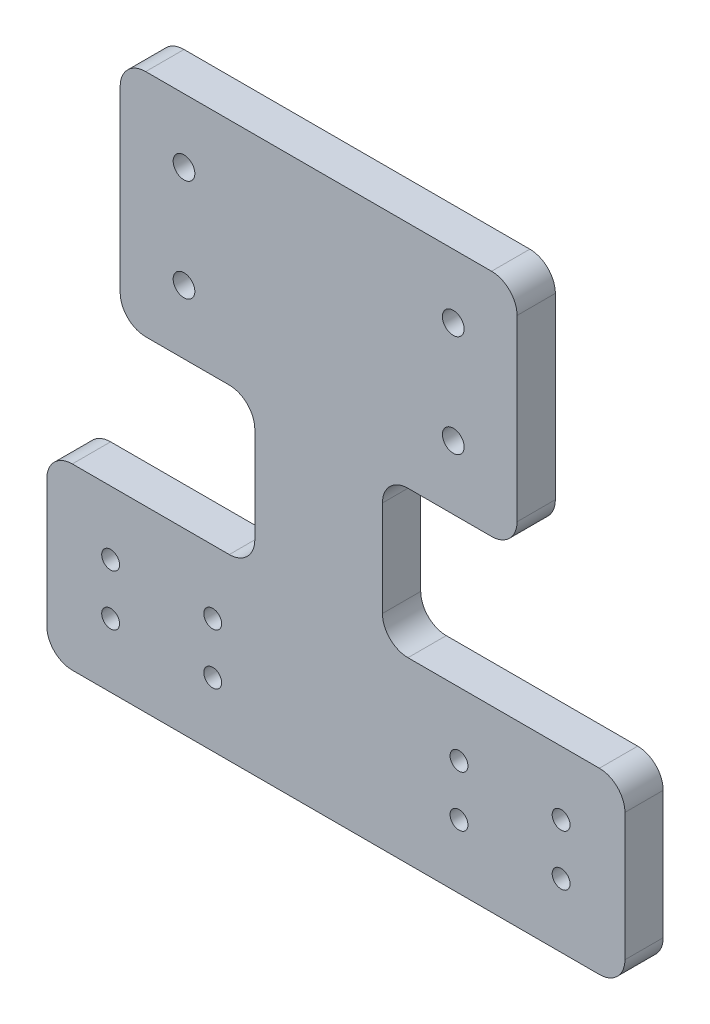
SolidWorks part; units mm, degrees
ref_plane "Front Plane" through (0, 0, 0) normal (0, 0, 1) x (1, 0, 0)
ref_plane "Top Plane" through (0, 0, 0) normal (0, 1, 0) x (1, 0, 0)
ref_plane "Right Plane" through (0, 0, 0) normal (1, 0, 0) x (0, 0, -1)
sketch "Sketch1" plane through (0, 0, 0) normal (0, 0, 1) x (1, 0, 0)
  line L0 (28.1, 15) -> (-28.1, 15) construction
  line L1 (-28.1, -15) -> (28.1, 15) construction
  line L2 (-28.1, 15) -> (-28.1, -15) construction
  line L3 (-28.1, -15) -> (28.1, -15) construction
  line L4 (-50, 20) -> (50, 20)
  line L5 (28.1, 15) -> (28.1, -15) construction
  line L6 (-50, 20) -> (-50, -80)
  line L7 (-50, -80) -> (50, -80)
  line L8 (50, 20) -> (50, -80)
  line L9 (-28.1, 15) -> (28.1, -15) construction
  line L10 (-50, 20) -> (50, -80) construction
  line L12 (-50, -80) -> (50, 20) construction
  dimension "D4" = 30
  dimension "D5" = 50
  dimension "D2" = 50
  dimension "D1" = 20
  dimension "D3" = 56.2
  dimension "D6" = 80
extrude "Boss-Extrude1" add sketch "Sketch1" along normal blind 6
sketch "Sketch2" plane through (0, 0, 0) normal (0, 0, 1) x (1, 0, 0)
  line L0 (28.1, 15) -> (-28.1, 15) construction
  line L1 (-28.1, -15) -> (28.1, 15) construction
  line L2 (-28.1, 15) -> (-28.1, -15) construction
  line L3 (-28.1, -15) -> (28.1, -15) construction
  line L4 (28.1, 15) -> (28.1, -15) construction
  line L5 (-28.1, 15) -> (28.1, -15) construction
  line L6 (-28.1, 0) -> (28.1, 0) construction
  line L7 (-17.9015, 8) -> (-19.5007, 10.77)
  line L8 (-19.5007, 10.77) -> (-22.6993, 10.77)
  line L9 (-22.6993, 10.77) -> (-24.2985, 8)
  line L10 (-24.2985, 8) -> (-22.6993, 5.23)
  line L11 (-22.6993, 5.23) -> (-19.5007, 5.23)
  line L12 (-19.5007, 5.23) -> (-17.9015, 8)
  line L13 (19.5007, 5.23) -> (17.9015, 8)
  line L14 (0, 15) -> (0, -15) construction
  line L15 (22.6993, 5.23) -> (19.5007, 5.23)
  line L16 (24.2985, 8) -> (22.6993, 5.23)
  line L17 (22.6993, 10.77) -> (24.2985, 8)
  line L18 (19.5007, 10.77) -> (22.6993, 10.77)
  line L19 (17.9015, 8) -> (19.5007, 10.77)
  line L20 (17.9015, -8) -> (19.5007, -10.77)
  line L21 (19.5007, -10.77) -> (22.6993, -10.77)
  line L22 (22.6993, -10.77) -> (24.2985, -8)
  line L23 (24.2985, -8) -> (22.6993, -5.23)
  line L24 (22.6993, -5.23) -> (19.5007, -5.23)
  line L25 (19.5007, -5.23) -> (17.9015, -8)
  line L26 (-19.5007, -5.23) -> (-17.9015, -8)
  line L27 (-22.6993, -5.23) -> (-19.5007, -5.23)
  line L28 (-24.2985, -8) -> (-22.6993, -5.23)
  line L29 (-22.6993, -10.77) -> (-24.2985, -8)
  line L30 (-19.5007, -10.77) -> (-22.6993, -10.77)
  line L31 (-17.9015, -8) -> (-19.5007, -10.77)
  circle A0 centre (-21.1, 8) radius 2.77 construction
  circle A1 centre (21.1, 8) radius 2.77 construction
  circle A2 centre (21.1, -8) radius 2.77 construction
  circle A3 centre (-21.1, -8) radius 2.77 construction
  dimension "D3" = 5.54
  dimension "D1" = 56.2
  dimension "D2" = 30
extrude "Cut-Extrude1" cut sketch "Sketch2" along normal blind 2.5
sketch "Sketch3" plane through (0, 0, 0) normal (0, 0, -1) x (-1, 0, 0)
  line L0 (28.1, 15) -> (-28.1, 15) construction
  line L1 (-28.1, -15) -> (28.1, 15) construction
  line L2 (-28.1, 15) -> (-28.1, -15) construction
  line L3 (-28.1, -15) -> (28.1, -15) construction
  line L4 (28.1, 15) -> (28.1, -15) construction
  line L5 (-28.1, 15) -> (28.1, -15) construction
  line L6 (-28.1, 0) -> (28.1, 0) construction
  line L7 (-17.9015, 8) -> (-19.5007, 10.77) construction
  line L8 (-19.5007, 10.77) -> (-22.6993, 10.77) construction
  line L9 (-22.6993, 10.77) -> (-24.2985, 8) construction
  line L10 (-24.2985, 8) -> (-22.6993, 5.23) construction
  line L11 (-22.6993, 5.23) -> (-19.5007, 5.23) construction
  line L12 (-19.5007, 5.23) -> (-17.9015, 8) construction
  line L13 (19.5007, 5.23) -> (17.9015, 8) construction
  line L14 (0, 15) -> (0, -15) construction
  line L15 (22.6993, 5.23) -> (19.5007, 5.23) construction
  line L16 (24.2985, 8) -> (22.6993, 5.23) construction
  line L17 (22.6993, 10.77) -> (24.2985, 8) construction
  line L18 (19.5007, 10.77) -> (22.6993, 10.77) construction
  line L19 (17.9015, 8) -> (19.5007, 10.77) construction
  line L20 (17.9015, -8) -> (19.5007, -10.77) construction
  line L21 (19.5007, -10.77) -> (22.6993, -10.77) construction
  line L22 (22.6993, -10.77) -> (24.2985, -8) construction
  line L23 (24.2985, -8) -> (22.6993, -5.23) construction
  line L24 (22.6993, -5.23) -> (19.5007, -5.23) construction
  line L25 (19.5007, -5.23) -> (17.9015, -8) construction
  line L26 (-19.5007, -5.23) -> (-17.9015, -8) construction
  line L27 (-22.6993, -5.23) -> (-19.5007, -5.23) construction
  line L28 (-24.2985, -8) -> (-22.6993, -5.23) construction
  line L29 (-22.6993, -10.77) -> (-24.2985, -8) construction
  line L30 (-19.5007, -10.77) -> (-22.6993, -10.77) construction
  line L31 (-17.9015, -8) -> (-19.5007, -10.77) construction
  circle A0 centre (-21.1, 8) radius 2.77 construction
  circle A1 centre (21.1, 8) radius 2.77 construction
  circle A2 centre (21.1, -8) radius 2.77 construction
  circle A3 centre (-21.1, -8) radius 2.77 construction
  circle A4 centre (-21.1, 8) radius 1.7
  circle A5 centre (21.1, 8) radius 1.7
  circle A6 centre (21.1, -8) radius 1.7
  circle A7 centre (-21.1, -8) radius 1.7
  dimension "D3" = 5.54
  dimension "D4" = 3.4
  dimension "D1" = 56.2
  dimension "D2" = 30
extrude "Cut-Extrude2" cut sketch "Sketch3" against normal up to surface (6 mm away) up to face at (0, -30, 6)
sketch "Sketch4" plane through (0, 0, 0) normal (0, 0, -1) x (-1, 0, 0)
  line L0 (-30, -29) -> (-30, -51) construction
  line L1 (0, 0) -> (0, -80) construction
  line L2 (50, -80) -> (-50, -80) construction
  line L3 (-38, -59) -> (-38, -51) construction
  line L4 (-22, -59) -> (-22, -51) construction
  line L5 (0, -40) -> (24.6, -40) construction
  line L6 (-10, -65) -> (-50, -65) construction
  line L7 (-10, -65) -> (-10, -15) construction
  line L8 (-10, -15) -> (-50, -15) construction
  line L9 (-50, -65) -> (-50, -15) construction
  line L10 (-10, -65) -> (-50, -15) construction
  line L11 (-10, -15) -> (-50, -65) construction
  line L12 (32.6, -59) -> (32.6, -51) construction
  line L13 (24.6, -59) -> (24.6, -51) construction
  line L14 (16.6, -59) -> (16.6, -51) construction
  circle A0 centre (-38, -59) radius 2.3
  circle A1 centre (-38, -51) radius 2.3
  circle A2 centre (-22, -51) radius 2.3
  circle A3 centre (-22, -59) radius 2.3
  circle A4 centre (32.6, -59) radius 2.3
  circle A5 centre (16.6, -51) radius 2.3
  circle A6 centre (16.6, -59) radius 2.3
  circle A7 centre (32.6, -51) radius 2.3
  point P14 (-30, -40)
  point P32 (24.6, -55)
  dimension "D1" = 4.6
  dimension "D8" = 24.6
  dimension "D9" = 4.6
  dimension "D2" = 50
  dimension "D3" = 8
  dimension "D4" = 8
  dimension "D5" = 40
  dimension "D6" = 10
  dimension "D7" = 15
extrude "Cut-Extrude3" cut sketch "Sketch4" against normal blind 2.5
sketch "Sketch5" plane through (0, 0, 0) normal (0, 0, -1) x (-1, 0, 0)
  line L0 (-30, -59) -> (-30, -51) construction
  line L1 (-38, -59) -> (-38, -51) construction
  line L2 (-22, -59) -> (-22, -51) construction
  line L3 (0, 0) -> (0, -55) construction
  line L6 (-30, -59) -> (-30, -51) construction
  line L7 (-38, -59) -> (-38, -51) construction
  line L8 (-22, -59) -> (-22, -51) construction
  line L9 (0, -55) -> (24.6, -55) construction
  line L10 (32.6, -59) -> (32.6, -51) construction
  line L11 (24.6, -59) -> (24.6, -51) construction
  line L12 (16.6, -59) -> (16.6, -51) construction
  circle A0 centre (-38, -59) radius 1.4
  circle A1 centre (-38, -51) radius 1.4
  circle A2 centre (-22, -51) radius 1.4
  circle A3 centre (-22, -59) radius 1.4
  circle A8 centre (-38, -59) radius 2.3 construction
  circle A9 centre (-38, -51) radius 2.3 construction
  circle A10 centre (-22, -51) radius 2.3 construction
  circle A11 centre (-22, -59) radius 2.3 construction
  circle A12 centre (32.6, -59) radius 1.4
  circle A13 centre (16.6, -51) radius 1.4
  circle A14 centre (16.6, -59) radius 1.4
  circle A15 centre (32.6, -51) radius 1.4
  point P10 (-30, -55)
  point P32 (-30, -55)
  point P45 (24.6, -55)
  dimension "D1" = 2.8
  dimension "D2" = 4.6
  dimension "D4" = 2.8
  dimension "D3" = 8
  dimension "D5" = 24.6
extrude "Cut-Extrude4" cut sketch "Sketch5" against normal up to surface (6 mm away) up to face at (-19.4, 8, 6)
sketch "Sketch6" plane through (0, 0, 6) normal (0, 0, 1) x (1, 0, 0)
  line L0 (0, 20) -> (0, -80) construction
  line L1 (50, 20) -> (-50, 20) construction
  line L2 (-50, -80) -> (50, -80) construction
  line L3 (-31.1, -14) -> (-31.1, 14)
  line L4 (-27.1, 18) -> (27.1, 18)
  line L5 (-27.1, -18) -> (-14, -18)
  line L6 (-10, -22) -> (-10, -37)
  line L7 (-14, -41) -> (-38.6, -41)
  line L8 (-42.6, -45) -> (-42.6, -65)
  line L9 (-38.6, -69) -> (44, -69)
  line L10 (14, -41) -> (44, -41)
  line L11 (48, -65) -> (48, -45)
  line L12 (10, -22) -> (10, -37)
  line L13 (27.1, -18) -> (14, -18)
  line L14 (31.1, -14) -> (31.1, 14)
  line L16 (-50, 20) -> (50, 20)
  line L17 (-50, 20) -> (-50, -80)
  line L18 (-50, -80) -> (50, -80)
  line L19 (50, 20) -> (50, -80)
  circle A1 centre (-21.1, -8) radius 1.7 construction
  circle A2 centre (-16.6, -51) radius 1.4 construction
  circle A3 centre (-32.6, -51) radius 1.4 construction
  circle A4 centre (-32.6, -59) radius 1.4 construction
  circle A5 centre (-21.1, 8) radius 1.7 construction
  circle A6 centre (38, -51) radius 1.4 construction
  arc A7 (27.1, 18) -> (31.1, 14) centre (27.1, 14) cw
  arc A8 (31.1, -14) -> (27.1, -18) centre (27.1, -14) cw
  arc A9 (14, -18) -> (10, -22) centre (14, -22) ccw
  arc A10 (10, -37) -> (14, -41) centre (14, -37) ccw
  arc A11 (44, -41) -> (48, -45) centre (44, -45) cw
  arc A12 (48, -65) -> (44, -69) centre (44, -65) cw
  arc A13 (-38.6, -69) -> (-42.6, -65) centre (-38.6, -65) cw
  arc A14 (-42.6, -45) -> (-38.6, -41) centre (-38.6, -45) cw
  arc A15 (-14, -41) -> (-10, -37) centre (-14, -37) ccw
  arc A16 (-10, -22) -> (-14, -18) centre (-14, -22) ccw
  arc A17 (-27.1, -18) -> (-31.1, -14) centre (-27.1, -14) cw
  arc A18 (-31.1, 14) -> (-27.1, 18) centre (-27.1, 14) cw
  point P25 (0, -69)
  point P30 (0, 18)
  point P40 (31.1, 18)
  point P43 (31.1, -18)
  point P46 (10, -18)
  point P49 (10, -41)
  point P52 (48, -41)
  point P57 (-42.6, -69)
  point P60 (-42.6, -41)
  point P63 (-10, -41)
  point P66 (-10, -18)
  point P69 (-31.1, -18)
  point P72 (-31.1, 18)
  dimension "D1" = 10
  dimension "D2" = 10
  dimension "D4" = 10
  dimension "D5" = 10
  dimension "D6" = 10
  dimension "D8" = 10
  dimension "D9" = 4
  dimension "D3" = 10
  dimension "D7" = 10
extrude "Cut-Extrude5" cut sketch "Sketch6" against normal blind 10
